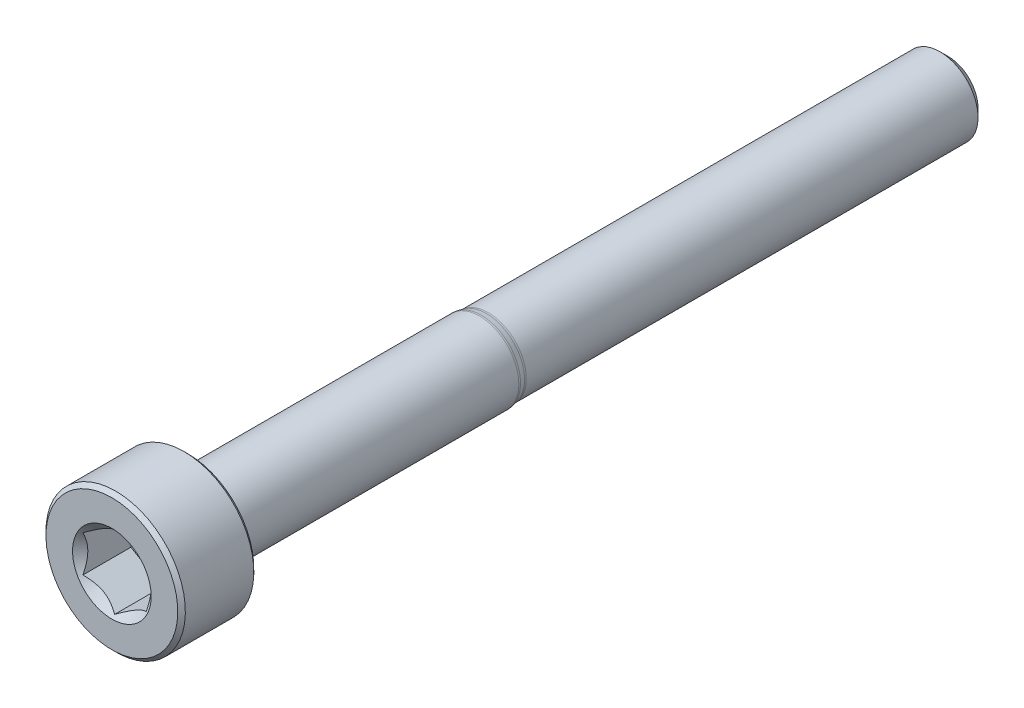
SolidWorks part; units mm, degrees
ref_plane "Front Plane" through (0, 0, 0) normal (0, 0, 1) x (1, 0, 0)
ref_plane "Top Plane" through (0, 0, 0) normal (0, 1, 0) x (1, 0, 0)
ref_plane "Right Plane" through (0, 0, 0) normal (1, 0, 0) x (0, 0, -1)
sketch "Sketch1" plane through (0, 0, 0) normal (1, 0, 0) x (0, 0, -1)
  line L0 (-16.5, 0) -> (16.5, 0) construction
  line L1 (16.5, 0) -> (16.5, 1.1752) construction
  line L2 (16.5, 1.1752) -> (16.1752, 1.5) construction
  line L3 (16.1752, 1.5) -> (16.125, 1.5) construction
  line L4 (16.125, 1.5) -> (-13.5, 1.5) construction
  line L5 (-13.5, 1.5) -> (-13.5, 2.75) construction
  line L6 (-13.5, 2.75) -> (-16.5, 2.75) construction
  line L7 (-16.5, 2.75) -> (-16.5, 0) construction
  line L8 (16.5, 1.1752) -> (16.5, 1.5) construction
  line L9 (16.4688, 1.5541) -> (16.7188, 1.1211) construction
  line L10 (16.7188, 1.1211) -> (16.9688, 1.5541) construction
  line L11 (16.9688, 1.5541) -> (16.4688, 1.5541) construction
  line L12 (16.7188, 1.5541) -> (16.7188, 1.5) construction
  line L13 (16.7188, 1.1211) -> (16.7188, 1.1752) construction
  line L14 (16.6875, 1.1752) -> (16.75, 1.1752) construction
  line L15 (16.5, 1.5) -> (16.9375, 1.5) construction
  line L16 (16.4844, 1.5271) -> (16.9531, 1.5271) construction
  line L17 (16.5, 0) -> (16.5, -1.5) construction
  line L18 (-13.65, 2.75) -> (-13.5, 2.6) construction
  line L19 (-16.35, 2.75) -> (-16.5, 2.6) construction
  line L20 (-13.5, 1.5) -> (-13.5, 0) construction
  line L21 (-13.5, 0.75) -> (-3.5, 0.75) construction
  line L22 (-3.5, 0.75) -> (6.5, 0.75) construction
  line L23 (6.5, 0.75) -> (16.5, 0.75) construction
  line L24 (-3.5, 0.75) -> (-3.5, 1.5) construction
  line L25 (-3.5, 1.5) -> (-3.5, 2.75) construction
  line L26 (6.5, 0.75) -> (6.5, 2.75) construction
  point P0 (-16.5, 1.25)
  point P3 (15.25, 1.5)
  point P4 (0, 0)
  point P18 (6.5, 1.5)
  point P22 (16.7188, 1.1752)
  point P24 (16.125, 1.5)
  point P25 (16.7188, 1.5)
  point P28 (16.7188, 1.5271)
  point P29 (15.25, -1.5)
  point P30 (-3.5, 1.5)
  point P31 (-15, 2.75)
  point P37 (-14.025, 2.75)
  point P38 (-16.275, 2.75)
  point P45 (-3.5, 0.75)
  point P46 (6.5, 0.75)
  point P49 (-1.5, 1.5)
  dimension "D1" = 45
  dimension "D2" = 0.0625
  dimension "D7" = 0.15
  dimension "D8" = 0.15
  dimension "D9" = 0.15
  dimension "D10" = 0.075
  dimension "D11" = 0.375
  dimension "Drive Size" = 2.5
  dimension "Head Diameter" = 5.5
  dimension "Head Height" = 3
  dimension "Thread Pitch" = 0.5
  dimension "Thread Dia" = 3
  dimension "Length" = 30
  dimension "D12" = 0.375
  dimension "D4" = 1.25
  dimension "Minimum Thread Length" = 18
  dimension "D3" = 12
sketch "Sketch2" plane through (0, 0, 0) normal (1, 0, 0) x (0, 0, -1)
  line L0 (-16.5, 0) -> (-16.5, 2.6)
  line L1 (-16.35, 2.75) -> (-13.65, 2.75)
  line L2 (-13.5, 2.6) -> (-13.5, 1.7041)
  line L4 (16.1752, 1.5) -> (16.5, 1.1752)
  line L5 (16.5, 1.1752) -> (16.5, 0)
  line L6 (-13.5, 2.75) -> (-16.5, 2.75) construction
  line L7 (16.5, 0) -> (-16.5, 0)
  line L8 (-16.35, 2.75) -> (-16.5, 2.6) construction
  line L10 (-16.35, 2.75) -> (-16.5, 2.6)
  line L14 (-13.65, 2.75) -> (-13.5, 2.6) construction
  line L16 (-13.65, 2.75) -> (-13.5, 2.6)
  line L17 (-13.5, 1.5) -> (-13.5, 2.75) construction
  line L18 (-13.35, 1.5541) -> (-1.9965, 1.5541)
  line L19 (-1.6506, 1.5) -> (16.1752, 1.5)
  line L20 (16.125, 1.5) -> (-13.5, 1.5) construction
  line L21 (-1.9234, 1.5469) -> (-1.7237, 1.5072)
  line L22 (16.9688, 1.5541) -> (16.4688, 1.5541) construction
  arc A1 (-13.5, 1.7041) -> (-13.35, 1.5541) centre (-13.35, 1.7041) ccw
  arc A2 (-1.9965, 1.5541) -> (-1.9234, 1.5469) centre (-1.9965, 1.1791) cw
  arc A3 (-1.7237, 1.5072) -> (-1.6506, 1.5) centre (-1.6506, 1.875) ccw
  point P39 (-1.6875, 1.5)
  dimension "D3" = 0.15
  dimension "D6" = 0.375
  dimension "D4" = 11.25
  dimension "D5" = 0.1875
revolve "Revolve1" add sketch "Sketch2" angle 360 about L7
sketch "Sketch3" plane through (0, 0, 16.5) normal (0, 0, 1) x (1, 0, 0)
  line L1 (1.25, -0.7217) -> (1.25, 0.7217)
  line L2 (1.25, 0.7217) -> (0, 1.4434)
  line L3 (0, 1.4434) -> (-1.25, 0.7217)
  line L4 (-1.25, 0.7217) -> (-1.25, -0.7217)
  line L5 (-1.25, -0.7217) -> (0, -1.4434)
  line L6 (0, -1.4434) -> (1.25, -0.7217)
  circle A0 centre (0, 0) radius 1.25 construction
  circle A1 centre (0, 0) radius 2.75 construction
  circle A2 centre (0, 0) radius 2.75 construction
  circle A3 centre (0, 0) radius 1.4434 construction
  dimension "D1" = 2.8868
extrude "Cut-Extrude1" cut sketch "Sketch3" against normal offset from surface (2 mm away) 1 up to face at (0, 2.6, 13.5)
sketch "Sketch4" plane through (0, 0, 16.5) normal (0, 0, 1) x (1, 0, 0)
  circle A0 centre (0, 0) radius 1.5516
  dimension "D1" = 3.1033
extrude "Cut-Extrude2" cut sketch "Sketch4" against normal up to vertex (1.5 mm away) draft 45 up to point (0, 2.75, 15)
sketch "Sketch11" plane through (0, 0, 0) normal (1, 0, 0) x (0, 0, -1)
  line L0 (-16.5, 0) -> (16.5, 0) construction
  line L1 (-16.5, 0) -> (16.5, 0) construction
  line L2 (-12, 0) -> (-12, 1.5) construction
  line L3 (16.125, 1.5) -> (-13.5, 1.5) construction
  line L4 (-3.4965, 0) -> (-3.4965, 1.5) construction
  point P2 (-12, 0)
  point P3 (-3.4965, 0)
  dimension "D1" = 1.5
  dimension "D2" = 1.5
sketch "Sketch6" [suppressed] plane through (0, 0, -16.5) normal (0, 0, -1) x (-1, 0, 0)
  circle A0 centre (0, 0) radius 1.5
curve "Helix/Spiral1" [suppressed] pitch 0.5 height 18.5 turns 37
sketch "Sketch10" [suppressed] plane through (0, 0, 0) normal (1, 0, 0) x (0, 0, -1)
  line L0 (-1.5, -1.5) -> (-1.5, 1.5)
  line L2 (-16.5, 0) -> (16.5, 0) construction
  point P3 (-1.5, 0)
split "Split1" [suppressed] bodies to split 106
sketch "Sketch7" [suppressed] plane through (0, 0, 0) normal (1, 0, 0) x (0, 0, -1)
  line L0 (16.4844, 1.5271) -> (16.9531, 1.5271)
  line L1 (16.9531, 1.5271) -> (16.75, 1.1752)
  line L2 (16.75, 1.1752) -> (16.6875, 1.1752)
  line L3 (16.6875, 1.1752) -> (16.4844, 1.5271)
sweep "Cut-Sweep1" [suppressed] cut profiles "Sketch7" path "Helix/Spiral1"
sketch "Sketch8" [suppressed] plane through (0, 0, 0) normal (1, 0, 0) x (0, 0, -1)
  line L0 (-13.5, 0) -> (-13.5, 1.5)
  line L2 (-13.5, 1.5) -> (-1.5, 1.5)
  line L4 (-1.5, 1.5) -> (-0.634, 0)
  line L5 (-0.634, 0) -> (-13.5, 0)
  line L6 (16.125, 1.5) -> (-13.5, 1.5) construction
  line L7 (-16.5, 0) -> (16.5, 0) construction
  dimension "D1" = 60
  dimension "D2" = 18
revolve "Revolve2" [suppressed] add sketch "Sketch8" angle 360 about L5
equation "\"D2@Sketch1\" = \"Thread Pitch@Sketch1\" / 8"
equation "\"D4@Helix/Spiral1\" = \"Thread Pitch@Sketch1\""
equation "\"D7@Sketch1\" = \"Head Height@Sketch1\" * .05"
equation "\"D8@Sketch1\"=\"D7@Sketch1\""
equation "\"D9@Sketch1\"=\"D7@Sketch1\""
equation "\"D10@Sketch1\"=\"D7@Sketch1\"/2"
equation "\"D11@Sketch1\"=\"D10@Sketch1\"*5"
equation "\"D4@Sketch1\"=\"Thread Pitch@Sketch1\"*2.5"
equation "\"D12@Sketch1\"=\"Thread Pitch@Sketch1\"*.75"
equation "\"D3@Helix/Spiral1\"=\"Minimum Thread Length@Sketch1\"+\"Thread Pitch@Sketch1\""
equation "\"D2@Sketch8\"=\"Minimum Thread Length@Sketch1\""
equation "\"D3@Sketch2\"=\"Thread Dia@Sketch1\"*0.05"
equation "\"D5@Sketch2\"=\"D12@Sketch1\"*0.5"
equation "\"D6@Sketch2\"=\"Thread Dia@Sketch1\"*0.125"
equation "\"D1@Sketch11\"=\"D3@Sketch1\"*0.125"
equation "\"D2@Sketch11\"=\"D1@Sketch11\""
equation "\"D1@Sketch4\"=\"D1@Sketch3\"*1.075"
